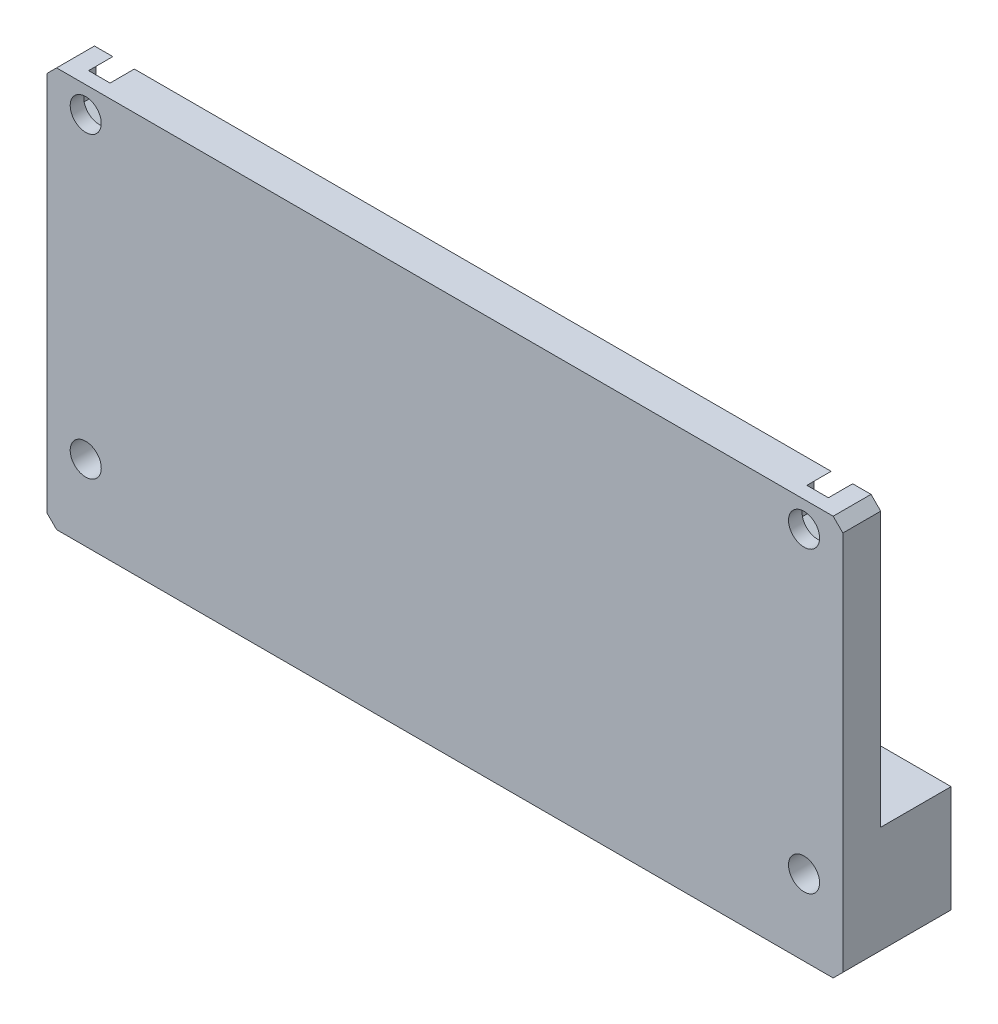
SolidWorks part; units mm, degrees
ref_plane "Front Plane" through (0, 0, 0) normal (0, 0, 1) x (1, 0, 0)
ref_plane "Top Plane" through (0, 0, 0) normal (0, 1, 0) x (1, 0, 0)
ref_plane "Right Plane" through (0, 0, 0) normal (1, 0, 0) x (0, 0, -1)
sketch "Sketch1" plane through (0, 0, 0) normal (0, 0, 1) x (1, 0, 0)
  line L0 (1, 11.6) -> (0, 10.6) construction
  line L1 (81, 11.6) -> (1, 11.6) construction
  line L2 (82, 10.6) -> (81, 11.6) construction
  line L3 (78, -21.813) -> (-11.5362, -21.813) construction
  line L4 (1, 11.6) -> (0, 10.6)
  line L5 (81, 11.6) -> (1, 11.6)
  line L6 (82, 10.6) -> (81, 11.6)
  line L7 (82, -36.852) -> (0, -36.852) construction
  line L8 (82, -36.852) -> (0, -36.852)
  line L9 (82, -36.852) -> (82, 10.6)
  line L10 (0, 10.6) -> (0, -36.852)
  line L11 (4, 8.9396) -> (4, -41.6656) construction
  circle A0 centre (4, 8.9396) radius 1.6 construction
  circle A1 centre (78, 8.9396) radius 1.6 construction
  circle A2 centre (4, -29.89) radius 1.6 construction
  circle A3 centre (4, 8.9396) radius 1.6
  circle A4 centre (78, 8.9396) radius 1.6
  circle A8 centre (78, -21.813) radius 1.6 construction
  circle A9 centre (78, -21.813) radius 1.6
  circle A10 centre (4, -21.813) radius 1.6
  dimension "D1" = 3.2
  dimension "D2" = 0
extrude "Boss-Extrude1" add sketch "Sketch1" along normal blind 11.15 contours A3 | L5 L4 L10 L8 L9 L6 | A9 | A4 | A10 region at (4, 8.9396, 0)
sketch "Sketch2" plane through (0, 0, 0) normal (0, 0, -1) x (-1, 0, 0)
  line L0 (0, -49.6) -> (-82, -49.6) construction
  line L1 (0, -49.6) -> (-82, -49.6) construction
  line L2 (-82, -54.6) -> (0, -54.6)
  line L3 (-82, -29.6) -> (0, -29.6)
  line L4 (-82, -36.852) -> (-82, 10.6) construction
  line L5 (0, 10.6) -> (0, -36.852) construction
  line L6 (-82, -36.852) -> (0, -36.852) construction
  line L7 (0, -29.6) -> (0, -36.852)
  line L8 (-82, -36.852) -> (-82, -29.6)
  line L9 (-82, -36.852) -> (0, -36.852)
  dimension "D1" = 5
  dimension "D2" = 25
extrude "Cut-Extrude1" cut sketch "Sketch2" against normal blind 8 contours L3 L7 L9 L8
sketch "Sketch3" plane through (0, -29.6, 0) normal (0, -1, 0) x (1, 0, 0)
  line L0 (10.85, 4) -> (10.85, 0)
  line L1 (14.15, 4) -> (14.15, 0)
  line L2 (16.75, 4) -> (16.75, 0)
  line L3 (23.25, 4) -> (23.25, 0)
  line L4 (0, 0) -> (82, 0)
  line L5 (82, 0) -> (82, 8)
  line L6 (82, 8) -> (0, 8)
  line L7 (0, 8) -> (0, 0)
  line L8 (10.85, 0) -> (14.15, 0)
  line L9 (82, 0) -> (82, 8)
  line L10 (82, 8) -> (0, 8)
  line L11 (0, 8) -> (0, 0)
  line L12 (25.85, 4) -> (25.85, 0)
  line L13 (29.15, 4) -> (29.15, 0)
  line L14 (25.85, 0) -> (82, 0)
  line L15 (16.75, 0) -> (23.25, 0)
  arc A0 (14.15, 4) -> (10.85, 4) centre (12.5, 4) ccw
  arc A1 (23.25, 4) -> (16.75, 4) centre (20, 4) ccw
  arc A2 (29.15, 4) -> (25.85, 4) centre (27.5, 4) ccw
  line M5 (0, 0) -> (82, 0)
  dimension "D2" = 3.3
  dimension "D3" = 3.3
  dimension "D4" = 15
  dimension "D5" = 7.5
  dimension "D6" = 6.5
  dimension "D7" = 20
  dimension "D1" = 0
extrude "Cut-Extrude2" cut sketch "Sketch3" against normal up to next contours L13 A2 L12 M5 | A0 L0 L8 L1 | A1 L2 L15 L3 region at (27.5, -29.6, 2.6608)
sketch "Sketch4" plane through (0, 11.6, 0) normal (0, 1, 0) x (1, 0, 0)
  line L0 (9.25, -4) -> (9.25, 0)
  line L1 (10.85, 0) -> (1, 0) construction
  line L2 (15.75, -4) -> (15.75, 0)
  line L3 (16.75, 0) -> (14.15, 0) construction
  line L4 (15.75, 0) -> (9.25, 0)
  line L5 (24.25, -4) -> (24.25, 0)
  line L6 (25.85, 0) -> (23.25, 0) construction
  line L7 (24.25, 0) -> (30.75, 0)
  line L8 (81, 0) -> (29.15, 0) construction
  line L9 (30.75, 0) -> (30.75, -4)
  arc A0 (10.85, -4) -> (14.15, -4) centre (12.5, -4) ccw construction
  arc A1 (25.85, -4) -> (29.15, -4) centre (27.5, -4) ccw construction
  arc A2 (10.85, -4) -> (14.15, -4) centre (12.5, -4) ccw construction
  arc A3 (25.85, -4) -> (29.15, -4) centre (27.5, -4) ccw construction
  arc A4 (9.25, -4) -> (15.75, -4) centre (12.5, -4) ccw
  arc A5 (24.25, -4) -> (30.75, -4) centre (27.5, -4) ccw
  dimension "D1" = 6.5
  dimension "D2" = 6.5
extrude "Cut-Extrude3" cut sketch "Sketch4" against normal offset from surface (31.7 mm away) 9.5 up to face at (25.25, -29.6, 2.9094)
sketch "Sketch6" plane through (0, 11.6, 0) normal (0, 1, 0) x (1, 0, 0)
  line L0 (15.75, -4) -> (15.75, 0) construction
  line L1 (24.25, 0) -> (24.25, -4) construction
  line L2 (15.75, -4) -> (15.75, 0)
  line L3 (24.25, 0) -> (24.25, -4)
  line L4 (12.5, -7.25) -> (0, -7.25)
  line L5 (0, -11.15) -> (0, 0) construction
  line L6 (0, -7.25) -> (0, 1.0612)
  line L7 (0, 1.0612) -> (15.75, 1.0612)
  line L8 (15.75, 1.0612) -> (15.75, 0)
  line L9 (27.5, -7.25) -> (41, -7.25)
  line L10 (41, -7.25) -> (41, 0)
  line L11 (81, 0) -> (30.75, 0) construction
  line L12 (41, 0) -> (24.25, 0)
  arc A0 (9.25, -4) -> (15.75, -4) centre (12.5, -4) ccw construction
  arc A1 (24.25, -4) -> (30.75, -4) centre (27.5, -4) ccw construction
  arc A2 (12.5, -7.25) -> (15.75, -4) centre (12.5, -4) ccw
  arc A3 (24.25, -4) -> (27.5, -7.25) centre (27.5, -4) ccw
  dimension "D1" = 41
extrude "Cut-Extrude5" cut sketch "Sketch6" against normal offset from surface (29.2 mm away) 12 up to face at (25.25, -29.6, 2.9094)
ref_plane "Plane1" through (41, 0, 0) normal (-1, 0, 0) x (0, 0, 1)
mirror "Mirror1" about plane through (41, 0, 0) normal (-1, 0, 0) of "Cut-Extrude5", "Cut-Extrude3", "Cut-Extrude2", "Cut-Extrude1"
sketch "Sketch8" plane through (0, 0, 8) normal (0, 0, -1) x (-1, 0, 0)
  line L4 (-82, -29.6) -> (-82, -36.852)
  line L5 (-82, -36.852) -> (0, -36.852)
  line L6 (0, -36.852) -> (0, -29.6)
  line L7 (0, -29.6) -> (-82, -29.6)
  line L8 (-82, -29.6) -> (-82, -36.852)
  line L9 (-82, -36.852) -> (0, -36.852)
  line L10 (0, -36.852) -> (0, -29.6)
  line L11 (0, -29.6) -> (-82, -29.6)
  dimension "D1" = 0
extrude "Cut-Extrude6" cut sketch "Sketch8" against normal through all
chamfer "Chamfer1" distance 1 angle 45 2 edges at (82, -29.6, 5.575) (0, -29.6, 5.575)
sketch "Sketch9" plane through (0, 0, 0) normal (-1, 0, 0) x (0, 0, 1)
  line L2 (7.25, 11.6) -> (0, 2.4)
  line L3 (0, 11.6) -> (7.25, 11.6)
sketch "Sketch12" plane through (0, 11.6, 0) normal (0, 1, 0) x (1, 0, 0)
  line L0 (16.75, -4) -> (16.75, 0)
  line L1 (16.75, 0) -> (18, 0)
  line L2 (23.25, 0) -> (23.25, -4)
  line L5 (22, 0) -> (23.25, 0)
  line L6 (58.75, -4) -> (58.75, 0)
  line L7 (58.75, 0) -> (60, 0)
  line L8 (65.25, 0) -> (65.25, -4) construction
  line L9 (65.25, 0) -> (65.25, -4)
  line L10 (60, 0) -> (60.11, -3.0846)
  line L11 (18, 0) -> (18.11, -3.0846)
  line L12 (64, 0) -> (65.25, 0)
  line L13 (22, 0) -> (21.89, -3.0846)
  line L15 (64, 0) -> (63.89, -3.0846)
  arc A0 (16.75, -4) -> (23.25, -4) centre (20, -4) ccw construction
  arc A1 (58.75, -4) -> (65.25, -4) centre (62, -4) ccw construction
  arc A2 (16.75, -4) -> (23.25, -4) centre (20, -4) ccw
  arc A3 (58.75, -4) -> (65.25, -4) centre (62, -4) ccw
  arc A4 (18.11, -3.0846) -> (21.89, -3.0846) centre (20, -4) ccw
  arc A5 (60.11, -3.0846) -> (63.89, -3.0846) centre (62, -4) ccw
  dimension "D1" = 1.25
  dimension "D2" = 4.2
  dimension "D3" = 1.25
  dimension "D4" = 1.25
  dimension "D5" = 1.25
extrude "Boss-Extrude2" add sketch "Sketch12" against normal offset from surface (19.2 mm away) 10 up to face at (41, -17.6, 3.9744)
chamfer "Chamfer3" distance 1.1 angle 45 3 edges at (58.75, -7.6, 2) (65.25, -7.6, 2) (62, -7.6, 7.25)
chamfer "Chamfer4" distance 1.1 angle 45 3 edges at (16.75, -7.6, 2) (23.25, -7.6, 2) (20, -7.6, 7.25)
extrude "Cut-Extrude12" cut sketch "Sketch9" against normal through all and the other way through all flip side to cut contours L3 L2
fillet "Fillet3" radius 15 4 edges at (16.875, 2.4, 0) (23.125, 2.4, 0) (58.875, 2.4, 0) (65.125, 2.4, 0)
sketch "Sketch13" plane through (0, 0, 0) normal (0, 0, -1) x (-1, 0, 0)
  line L1 (-78, -18.513) -> (-80.8579, -20.163)
  line L2 (-80.8579, -20.163) -> (-80.8579, -23.463)
  line L3 (-80.8579, -23.463) -> (-78, -25.113)
  line L4 (-78, -25.113) -> (-75.1421, -23.463)
  line L5 (-75.1421, -23.463) -> (-75.1421, -20.163)
  line L6 (-75.1421, -20.163) -> (-78, -18.513)
  line L7 (-4, -18.513) -> (-6.8579, -20.163)
  line L8 (-6.8579, -20.163) -> (-6.8579, -23.463)
  line L9 (-6.8579, -23.463) -> (-4, -25.113)
  line L10 (-4, -25.113) -> (-1.1421, -23.463)
  line L11 (-1.1421, -23.463) -> (-1.1421, -20.163)
  line L12 (-1.1421, -20.163) -> (-4, -18.513)
  circle A0 centre (-78, -21.813) radius 3.3 construction
  circle A1 centre (-4, -21.813) radius 3.3 construction
  dimension "D1" = 6.6
  dimension "D2" = 6.6
extrude "Cut-Extrude13" cut sketch "Sketch13" against normal blind 4
sketch "Sketch14" plane through (0, 0, 7.25) normal (0, 0, -1) x (-1, 0, 0)
  line L1 (-78, 12.2396) -> (-80.8579, 10.5896)
  line L2 (-80.8579, 10.5896) -> (-80.8579, 7.2896)
  line L3 (-80.8579, 7.2896) -> (-78, 5.6396)
  line L4 (-78, 5.6396) -> (-75.1421, 7.2896)
  line L5 (-75.1421, 7.2896) -> (-75.1421, 10.5896)
  line L6 (-75.1421, 10.5896) -> (-78, 12.2396)
  circle A0 centre (-78, 8.9396) radius 3.3 construction
  dimension "D1" = 6.6
extrude "Cut-Extrude14" cut sketch "Sketch14" against normal blind 2.5
mirror "Mirror2" about plane through (41, 0, 0) normal (-1, 0, 0) of "Cut-Extrude14"
